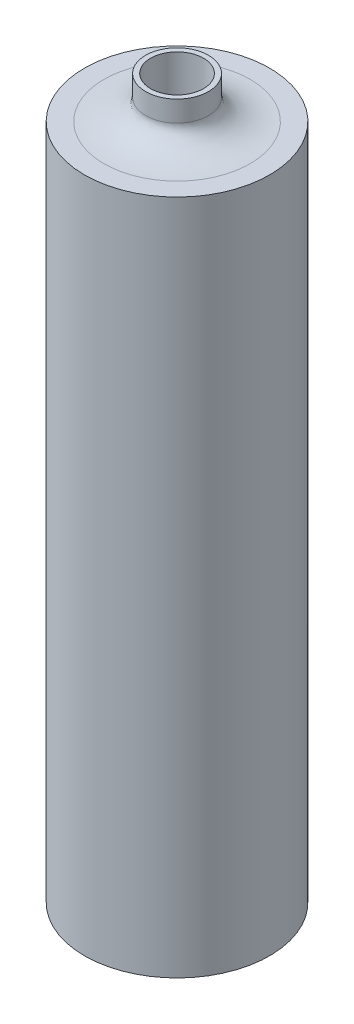
SolidWorks part; units mm, degrees
material "ABS PC"
ref_plane "Alzado" through (0, 0, 0) normal (0, 0, 1) x (1, 0, 0)
ref_plane "Planta" through (0, 0, 0) normal (0, 1, 0) x (1, 0, 0)
ref_plane "Vista lateral" through (0, 0, 0) normal (1, 0, 0) x (0, 0, -1)
sketch "Sketch1" plane through (0, 0, 0) normal (0, 1, 0) x (1, 0, 0)
  circle A0 centre (0, 0) radius 22.225
  circle A1 centre (0, 0) radius 19.05
  dimension "D1" = 44.45
  dimension "D2" = 38.1
extrude "Boss-Extrude1" add sketch "Sketch1" along normal blind 160
sketch "Sketch3" plane through (0, 0, 0) normal (0, -1, 0) x (1, 0, 0)
  circle A0 centre (0, 0) radius 22.225
  circle A1 centre (0, 0) radius 6.35
  dimension "D1" = 12.7
extrude "Boss-Extrude2" add sketch "Sketch3" against normal blind 2.4 from surface starting at face at (0, 160, 22.225)
sketch "Sketch4" plane through (0, 162.4, 0) normal (0, 1, 0) x (-1, 0, 0)
  circle A0 centre (0, 0) radius 6.35
  circle A1 centre (0, 0) radius 7.55
  dimension "D1" = 1.2
extrude "Boss-Extrude3" add sketch "Sketch4" along normal blind 10
fillet "Fillet1" radius 10 1 edges at (0, 162.4, 7.55) second distance 5 first distance on face at (0, 162.4, 22.225)
